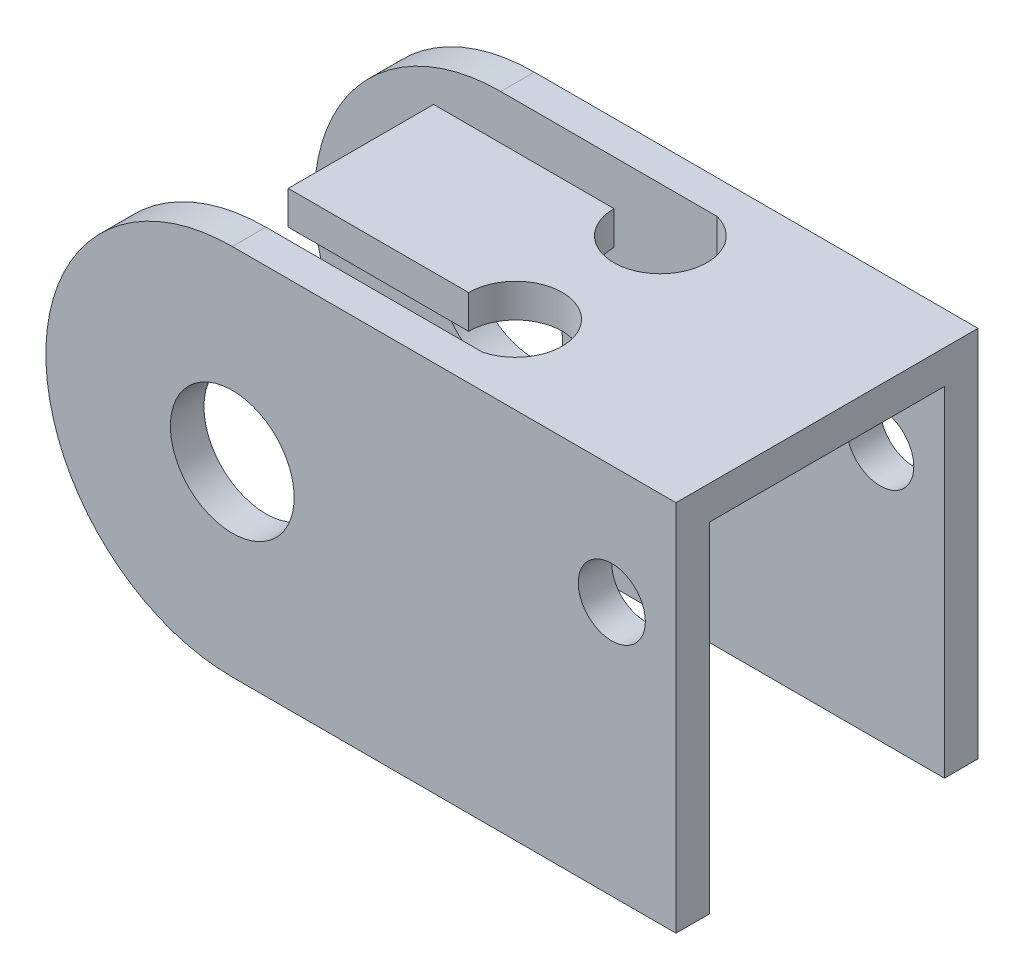
SolidWorks part; units mm, degrees
material "Plain Carbon Steel"
ref_plane "Front Plane" through (0, 0, 0) normal (0, 0, 1) x (1, 0, 0)
ref_plane "Top Plane" through (0, 0, 0) normal (0, 1, 0) x (1, 0, 0)
ref_plane "Right Plane" through (0, 0, 0) normal (1, 0, 0) x (0, 0, -1)
sketch "Sketch1" plane through (0, 0, 0) normal (0, 1, 0) x (1, 0, 0)
  line L1 (-4.0767, 5.1435) -> (4.0767, 5.1435)
  line L2 (-4.0767, 5.1435) -> (-4.0767, -5.1435)
  line L3 (-4.0767, -5.1435) -> (4.0767, -5.1435)
  line L4 (4.0767, 5.1435) -> (4.0767, -5.1435)
  line L5 (-4.0767, 5.1435) -> (4.0767, -5.1435) construction
  line L6 (-4.0767, -5.1435) -> (4.0767, 5.1435) construction
  point P0 (0, 0)
  dimension "D1" = 8.1534
  dimension "D2" = 10.287
extrude "Boss-Extrude1" add sketch "Sketch1" along normal blind 1.143
sketch "Sketch2" plane through (0, 0, 0) normal (0, 1, 0) x (1, 0, 0)
  line L0 (4.0767, -5.1435) -> (4.0767, 5.1435) construction
  line L1 (-11.7983, 2.4765) -> (-5.6515, 2.4765)
  line L2 (-11.7983, 2.4765) -> (-11.7983, -2.4765)
  line L3 (-11.7983, -2.4765) -> (-5.6515, -2.4765)
  line L5 (-11.7983, 2.4765) -> (-5.4096, -1.6215) construction
  line L6 (-11.7983, -2.4765) -> (-5.4096, 1.6215) construction
  line L7 (-4.0767, 5.1435) -> (-4.0767, -5.1435) construction
  line L8 (-4.0767, 5.1435) -> (-4.0767, 4.0513)
  line L10 (-4.0767, -4.0513) -> (-4.0767, -5.1435)
  line L11 (-4.0767, 5.1435) -> (4.0767, 5.1435)
  line L12 (4.0767, 5.1435) -> (4.0767, -5.1435)
  line L13 (4.0767, -5.1435) -> (-4.0767, -5.1435)
  arc A0 (-4.0767, -4.0513) -> (-5.6515, -2.4765) centre (-4.0641, -2.4639) ccw
  arc A1 (-5.6515, 2.4765) -> (-4.0767, 4.0513) centre (-4.0641, 2.4639) ccw
  point P0 (-7.9375, 0)
  dimension "D3" = 1.5875
  dimension "D1" = 4.953
  dimension "D2" = 15.875
  dimension "D4" = 1.5748
  dimension "D5" = 1.5748
  dimension "D6" = 2.667
  dimension "D7" = 1.5748
  dimension "D8" = 7.59
extrude "Boss-Extrude2" add sketch "Sketch2" along normal blind 1.143
sketch "Sketch3" plane through (0, 1.143, 0) normal (0, 1, 0) x (1, 0, 0)
  circle A0 centre (-4.0641, 2.4639) radius 1.5875
  circle A1 centre (-4.0641, -2.4639) radius 1.5875
extrude "Cut-Extrude1" cut sketch "Sketch3" against normal blind 1.143
sketch "Sketch4" plane through (0, 0, 5.1435) normal (0, 0, 1) x (1, 0, 0)
  line L1 (4.0767, 1.143) -> (-17.3863, 1.143)
  line L2 (4.0767, 1.143) -> (4.0767, -11.557)
  line L3 (4.0767, -11.557) -> (-17.3863, -11.557)
  line L4 (-17.3863, 1.143) -> (-17.3863, -11.557)
  dimension "D1" = 21.463
  dimension "D2" = 12.7
extrude "Boss-Extrude3" add sketch "Sketch4" against normal blind 1.143
fillet "Fillet1" 2 edges at (-17.3863, 1.143, 4.572) (-17.3863, -11.557, 4.572) type full round first side face at (-6.3504, 1.143, 0.3489) second side face at (-6.6548, -11.557, 4.572) middle face at (-17.3863, -5.207, 4.572)
hole_wizard "#19 (0.166) Diameter Hole1" positions "Sketch7" profile "Sketch8" hole size "#19" standard "ANSI Inch" end condition through all
sketch "Sketch7" plane through (0, 0, 5.1435) normal (0, 0, 1) x (1, 0, 0)
  point P0 (-11.0363, -5.207)
sketch "Sketch8" plane through (-11.0363, -5.207, 5.1435) normal (1, 0, 0) x (0, -1, 0)
  line L0 (0, 0) -> (0, 10.287)
  line L1 (0, 10.287) -> (2.1082, 10.287)
  line L2 (2.1082, 10.287) -> (2.1082, 0)
  line L5 (2.1082, 0) -> (0, 0)
  line L11 (0, -6.35) -> (0, 107.95) construction
  dimension "Thru Hole Dia." = 4.2164
  dimension "Thru Hole Depth" = 10.287
sketch "Sketch9" plane through (0, 0, 5.1435) normal (0, 0, 1) x (1, 0, 0)
  circle A0 centre (1.8894, -2.8848) radius 1.143
  dimension "D1" = 2.286
extrude "Cut-Extrude2" cut sketch "Sketch9" against normal up to vertex (1.143 mm away) up to point (4.0767, -11.557, 4.0005)
mirror "Mirror1" about plane through (0, 0, 0) normal (0, 0, 1) of "Fillet1", "Boss-Extrude3", "#19 (0.166) Diameter Hole1", "Cut-Extrude2"
